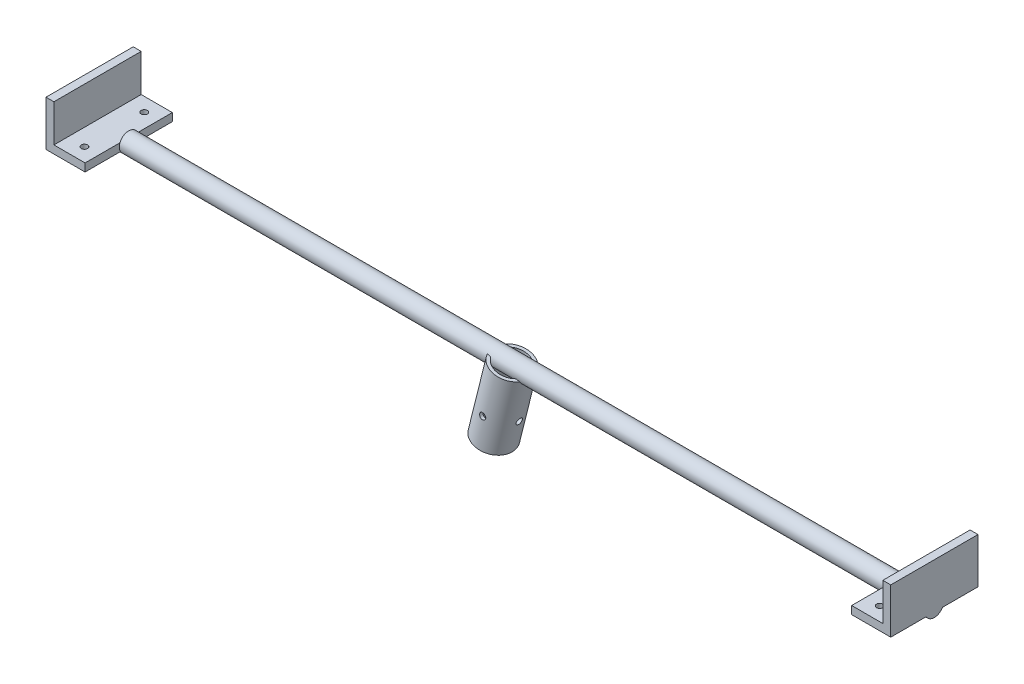
SolidWorks part; units mm, degrees
material "Alloy Steel"
ref_plane "Front" through (0, 0, 0) normal (0, 0, 1) x (1, 0, 0)
ref_plane "Top" through (0, 0, 0) normal (0, 1, 0) x (1, 0, 0)
ref_plane "Right" through (0, 0, 0) normal (1, 0, 0) x (0, 0, -1)
sketch "Sketch1" plane through (0, 0, 0) normal (1, 0, 0) x (0, 0, -1)
  circle A0 centre (0, 0) radius 7.5
  dimension "D1" = 15
extrude "Boss-Extrude1" add sketch "Sketch1" along normal blind 338.85
sketch "Sketch4" plane through (338.85, 0, 0) normal (1, 0, 0) x (0, 0, -1)
  line L0 (-7, 2.6926) -> (7, 2.6926)
  arc A0 (7, 2.6926) -> (-7, 2.6926) centre (0, 0) ccw
  dimension "D1" = 15
  dimension "D2" = 14
extrude "Cut-Extrude3" cut sketch "Sketch4" against normal blind 25 from offset 6.35 offset against normal yes
sketch "Sketch5" plane through (0, 2.6926, 0) normal (0, 1, 0) x (1, 0, 0)
  line L0 (332.5, -7) -> (332.5, 7) construction
  line L1 (307.5, 35) -> (332.5, 35)
  line L2 (307.5, 35) -> (307.5, -35)
  line L3 (307.5, -35) -> (332.5, -35)
  line L4 (332.5, 35) -> (332.5, -35)
  line L5 (307.5, 35) -> (332.5, -35) construction
  line L6 (307.5, -35) -> (332.5, 35) construction
  line L7 (307.5, -7) -> (307.5, 7) construction
  point P0 (320, 0)
  dimension "D1" = 70
extrude "Boss-Extrude2" add sketch "Sketch5" against normal blind 6.35
sketch "Sketch6" plane through (0, 2.6926, 0) normal (0, 1, 0) x (1, 0, 0)
  line L0 (332.5, 35) -> (332.5, -35)
  line L1 (332.5, 35) -> (338.85, 35)
  line L2 (332.5, -35) -> (338.85, -35)
  line L3 (338.85, 35) -> (338.85, -35)
  line L4 (338.85, -7.5) -> (338.85, 7.5) construction
extrude "Boss-Extrude3" add sketch "Sketch6" against normal blind 6.35 and the other way blind 30
hole_wizard "#8 (0.199) Diameter Hole1" positions "Sketch8" profile "Sketch7" hole size "#8" standard "ANSI Inch"
sketch "Sketch8" plane through (0, -3.6574, 0) normal (0, -1, 0) x (-1, 0, 0)
  line L0 (-338.85, 6.5478) -> (-338.85, -6.5478) construction
  line L1 (-307.5, -6.5478) -> (-307.5, -35) construction
  point P0 (-319, 24)
  point P2 (-319, -24)
  point P5 (-338.85, 0)
  dimension "D1" = 48
  dimension "D2" = 24
  dimension "D3" = 11.5
sketch "Sketch7" plane through (319, -3.6574, -24) normal (1, 0, 0) x (0, 0, -1)
  line L0 (0, 0) -> (0, 32.41)
  line L1 (0, 32.41) -> (2.5273, 32.41)
  line L2 (2.5273, 32.41) -> (2.5273, 0)
  line L5 (2.5273, 0) -> (0, 0)
  line L10 (0, 32.41) -> (-2.5273, 32.41) construction
  line L11 (0, -6.35) -> (0, 107.95) construction
  dimension "Hole Dia." = 5.0546
  dimension "Hole Depth" = 32.41
  dimension "Drill Angle" = 180
mirror "Mirror1" about plane through (0, 0, 0) normal (1, 0, 0) of "Boss-Extrude1", "Cut-Extrude3", "Boss-Extrude2", "Boss-Extrude3", "#8 (0.199) Diameter Hole1"
sketch "Sketch9" plane through (0, 0, 0) normal (0, 0, 1) x (1, 0, 0)
  line L0 (0, 0) -> (-117.4227, 0) construction
  line L1 (0, 0) -> (8.2085, 32.9226) construction
  dimension "D1" = 76
ref_plane "Plane1" through (0, 0, 0) normal (0.2419, 0.9703, 0) x (0.9703, -0.2419, 0)
sketch "Sketch10" plane through (0, 0, 0) normal (0.2419, 0.9703, 0) x (0.9703, -0.2419, 0)
  circle A0 centre (0, 0) radius 12.5
  circle A1 centre (0, 0) radius 15
  dimension "D1" = 25
  dimension "D2" = 30
extrude "Boss-Extrude4" add sketch "Sketch10" against normal blind 60
hole_wizard "#8 (0.199) Diameter Hole2" positions "3DSketch4" profile "Sketch12" hole size "#8" standard "ANSI Inch"
sketch3d "3DSketch4"
  point P0 (-8.6965, -33.9032, 14.9981)
  point P2 (6.0872, -37.5892, 0)
  dimension "D1" = 25
  dimension "D2" = 25
sketch "Sketch12" plane through (-8.6965, -33.9032, 14.9981) normal (0.7071, 0.7071, 0.0081) x (0.707, -0.7071, 0.0135)
  line L0 (0, 0) -> (0, 40)
  line L1 (0, 40) -> (2.5273, 40)
  line L2 (2.5273, 40) -> (2.5273, 0)
  line L5 (2.5273, 0) -> (0, 0)
  line L10 (0, 40) -> (-2.5273, 40) construction
  line L11 (0, -6.35) -> (0, 107.95) construction
  dimension "Hole Dia." = 5.0546
  dimension "Hole Depth" = 40
  dimension "Drill Angle" = 180
